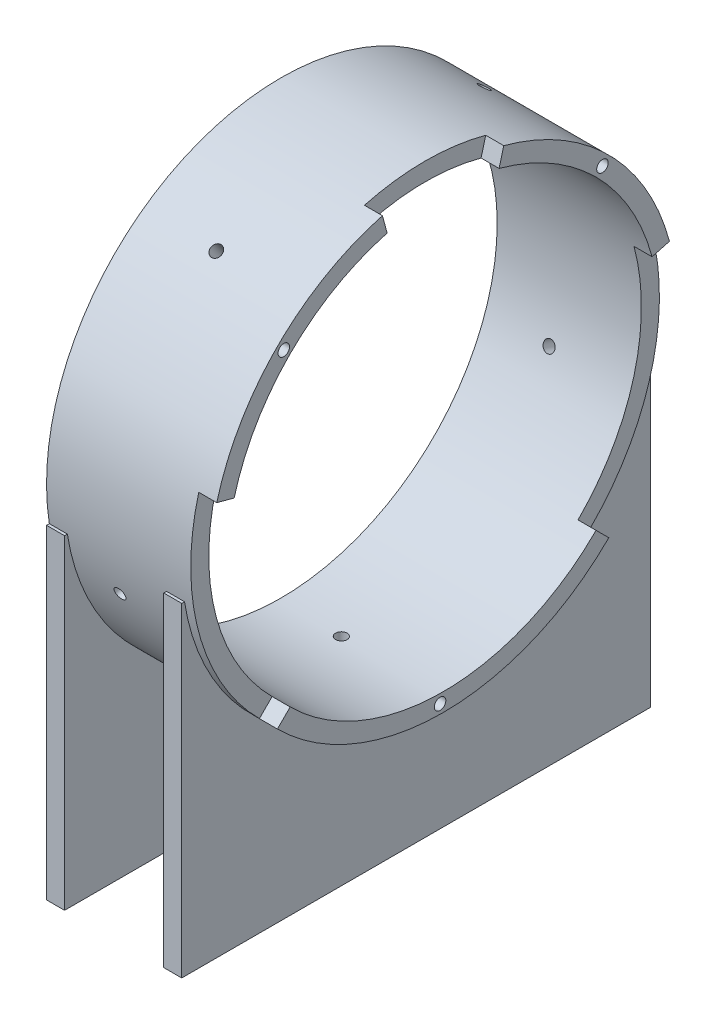
SolidWorks part; units mm, degrees
note: The reader was unsure of these and kept them because the rebuilt part matched: shared geometry of "Sketch1<3>".
material "Copper"
ref_plane "Front Plane" through (0, 0, 0) normal (0, 0, 1) x (1, 0, 0)
ref_plane "Top Plane" through (0, 0, 0) normal (0, 1, 0) x (1, 0, 0)
ref_plane "Right Plane" through (0, 0, 0) normal (1, 0, 0) x (0, 0, -1)
sketch "Sketch1" plane through (0, 0, 0) normal (1, 0, 0) x (0, 0, -1)
  circle A0 centre (0, 0) radius 240
  circle A1 centre (0, 0) radius 260
  point P4 (-152.8242, 210.3444)
  point P5 (0, -260)
  point P6 (152.8242, 210.3444)
  point P7 (247.2747, -80.3444)
  point P8 (-247.2747, -80.3444)
surface "Surface-Plane2" sketch "Sketch1"
extrude "Boss-Extrude1" add sketch "Sketch1<3>" along normal blind 180
sketch "Sketch1<3>" plane through (0, 0, 0) normal (1, 0, 0) x (0, 0, -1) same geometry as "Sketch1"
sketch "Sketch6" plane through (0, 0, 0) normal (1, 0, 0) x (0, 0, -1)
  line L0 (-260, -40) -> (-260, -400)
  line L1 (-260, -400) -> (260, -400)
  line L2 (260, -400) -> (260, -40)
  line L3 (256.9047, -40) -> (260, -40)
  line L5 (-260, -40) -> (-256.9047, -40)
  arc A1 (256.9047, -40) -> (-256.9047, -40) centre (0, 0) cw
  point P7 (256.9047, -40)
  point P11 (-256.9047, -40)
ref_plane "Plane1" through (150, 0, 0) normal (1, 0, 0) x (0, 0, -1)
sketch "Sketch11" plane through (150, 0, 0) normal (1, 0, 0) x (0, 0, -1)
  line L0 (-260, -40) -> (-260, -400)
  line L1 (-260, -400) -> (260, -400)
  line L2 (260, -400) -> (260, -40)
  line L3 (260, -40) -> (256.9047, -40)
  line L4 (-256.9047, -40) -> (-260, -40)
  arc A1 (-256.9047, -40) -> (256.9047, -40) centre (0, 0) ccw
  point P15 (-256.9047, -40)
  point P16 (256.9047, -40)
extrude "Boss-Extrude2" add sketch "Sketch6" along normal blind 20 contours L0 L1 L2 L3 A1 L5
extrude "Boss-Extrude3" add sketch "Sketch11" against normal blind 20 contours L0 L1 L2 L3 A1 L4
ref_plane "Plane3" through (70, 0, 0) normal (1, 0, 0) x (0, 0, -1)
sketch "Sketch16" plane through (70, 0, 0) normal (1, 0, 0) x (0, 0, -1)
  point P3 (-152.8242, 210.3444)
  point P4 (152.8242, 210.3444)
  point P6 (0, -260)
  point P8 (247.2747, -80.3444)
  point P10 (-247.2747, -80.3444)
hole_wizard "1/2-13 Tapped Hole6" positions "3DSketch10" profile "Sketch23" tap size "1/2-13" standard "ANSI Inch"
sketch3d "3DSketch10"
  point P0 (70.2979, -259.9761, 3.5286)
  point P2 (70, -80.3444, 247.2747)
  point P5 (70, -80.3444, 247.2747)
  point P7 (70, -80.3444, 247.2747)
  point P9 (69.9808, -76.5553, 248.4739)
  point P11 (70.1335, 208.1617, -155.7841)
  point P13 (70.1734, -83.043, -246.3815)
  point P15 (81.0465, 210.4143, 152.7279)
sketch "Sketch23" plane through (70.2979, -259.9761, 3.5286) normal (1, 0, 0) x (0, -0.0136, -0.9999)
  line L0 (0, 0) -> (0, 33.2195)
  line L1 (0, 33.2195) -> (5.3581, 30)
  line L2 (5.3581, 30) -> (5.3581, 40)
  line L3 (5.3581, 40) -> (6.35, 40)
  line L4 (6.35, 40) -> (6.35, 0)
  line L5 (6.35, 0) -> (0, 0)
  line L10 (0, 33.2195) -> (-5.3581, 30) construction
  line L11 (0, -6.35) -> (0, 107.95) construction
  dimension "Tap Drill Dia." = 10.7163
  dimension "Tap Drill Depth" = 30
  dimension "Thread Major Dia." = 12.7
  dimension "Thread Depth" = 40
  dimension "Drill Angle" = 118
ref_plane "Plane4" through (180, 0, 0) normal (1, 0, 0) x (0, 0, -1)
sketch "Sketch25" plane through (180, 0, 0) normal (1, 0, 0) x (0, 0, -1)
  line L0 (-169.7056, -169.7056) -> (-183.8478, -183.8478)
  line L1 (169.7056, -169.7056) -> (183.8478, -183.8478)
  line L2 (62.1166, 231.8222) -> (67.293, 251.1407)
  line L3 (-62.1166, 231.8222) -> (-67.293, 251.1407)
  line L4 (-231.8222, 62.1166) -> (-251.1407, 67.293)
  line L8 (231.8222, 62.1166) -> (251.1407, 67.293)
  circle A0 centre (0, 0) radius 260 construction
  arc A1 (-256.9047, -40) -> (256.9047, -40) centre (0, 0) ccw construction
  arc A2 (-231.8222, -62.1166) -> (-169.7056, -169.7056) centre (0, 0) ccw
  arc A3 (251.1407, -67.293) -> (251.1407, 67.293) centre (0, 0) ccw
  arc A4 (231.8222, -62.1166) -> (231.8222, 62.1166) centre (0, 0) ccw
  arc A5 (67.293, 251.1407) -> (-67.293, 251.1407) centre (0, 0) ccw
  arc A6 (62.1166, 231.8222) -> (-62.1166, 231.8222) centre (0, 0) ccw
  arc A7 (-251.1407, 67.293) -> (-251.1407, -67.293) centre (0, 0) ccw
  arc A8 (-231.8222, 62.1166) -> (-231.8222, -62.1166) centre (0, 0) ccw
  arc A9 (-251.1407, -67.293) -> (-183.8478, -183.8478) centre (0, 0) ccw
  arc A10 (169.7056, -169.7056) -> (231.8222, -62.1166) centre (0, 0) ccw
  circle A11 centre (0, 0) radius 240 construction
  arc A12 (183.8478, -183.8478) -> (251.1407, -67.293) centre (0, 0) ccw
extrude "Cut-Extrude1" cut sketch "Sketch25" against normal blind 20
ref_plane "Plane5" through (180, 0, 0) normal (1, 0, 0) x (0, 0, -1)
sketch "Sketch29" plane through (180, 0, 0) normal (1, 0, 0) x (0, 0, -1)
  line L2 (183.8478, 183.8478) -> (169.7056, 169.7056)
  line L3 (-183.8478, 183.8478) -> (-169.7056, 169.7056)
  line L6 (-169.7056, -169.7056) -> (-183.8478, -183.8478)
  line L7 (169.7056, -169.7056) -> (183.8478, -183.8478)
  point P3 (-176.7767, 176.7767)
  point P4 (176.7767, 176.7767)
  point P5 (-176.7767, -176.7767)
  point P6 (176.7767, -176.7767)
hole_wizard "1/2-13 Tapped Hole1" positions "3DSketch13" profile "Sketch31" tap size "1/2-13" standard "ANSI Inch"
sketch3d "3DSketch13"
  point P0 (180, 176.7767, -176.7767)
  point P3 (180, 176.7767, 176.7767)
  point P6 (180, -249.8673, 3.3572)
sketch "Sketch31" plane through (180, 176.7767, -176.7767) normal (0, 1, 0) x (0, 0, -1)
  line L0 (0, 0) -> (0, 53.2195)
  line L1 (0, 53.2195) -> (5.3581, 50)
  line L2 (5.3581, 50) -> (5.3581, 64.5)
  line L3 (5.3581, 64.5) -> (6.35, 64.5)
  line L4 (6.35, 64.5) -> (6.35, 0)
  line L5 (6.35, 0) -> (0, 0)
  line L10 (0, 53.2195) -> (-5.3581, 50) construction
  line L11 (0, -6.35) -> (0, 107.95) construction
  dimension "Tap Drill Dia." = 10.7163
  dimension "Tap Drill Depth" = 50
  dimension "Thread Major Dia." = 12.7
  dimension "Thread Depth" = 64.5
  dimension "Drill Angle" = 118
ref_plane "Plane6" through (0, -400, 0) normal (0, -1, 0) x (-1, 0, 0)
sketch "Sketch32" plane through (0, -400, 0) normal (0, -1, 0) x (-1, 0, 0)
  point P4 (-140, 250)
  point P5 (-10, 250)
  point P6 (-10, -250)
  point P11 (-140, -250)
hole_wizard "1/2-13 Tapped Hole7" positions "3DSketch14" profile "Sketch33" tap size "1/2-13" standard "ANSI Inch"
sketch3d "3DSketch14"
  point P0 (140, -400, 250)
  point P3 (10, -400, 250)
  point P6 (10, -400, -250)
  point P9 (140, -400, -250)
sketch "Sketch33" plane through (140, -400, 250) normal (1, 0, 0) x (0, 0, -1)
  line L0 (0, 0) -> (0, 49.1195)
  line L1 (0, 49.1195) -> (5.3581, 45.9)
  line L2 (5.3581, 45.9) -> (5.3581, 40)
  line L3 (5.3581, 40) -> (6.35, 40)
  line L4 (6.35, 40) -> (6.35, 0)
  line L5 (6.35, 0) -> (0, 0)
  line L10 (0, 49.1195) -> (-5.3581, 45.9) construction
  line L11 (0, -6.35) -> (0, 107.95) construction
  dimension "Tap Drill Dia." = 10.7163
  dimension "Tap Drill Depth" = 45.9
  dimension "Thread Major Dia." = 12.7
  dimension "Thread Depth" = 40
  dimension "Drill Angle" = 118
